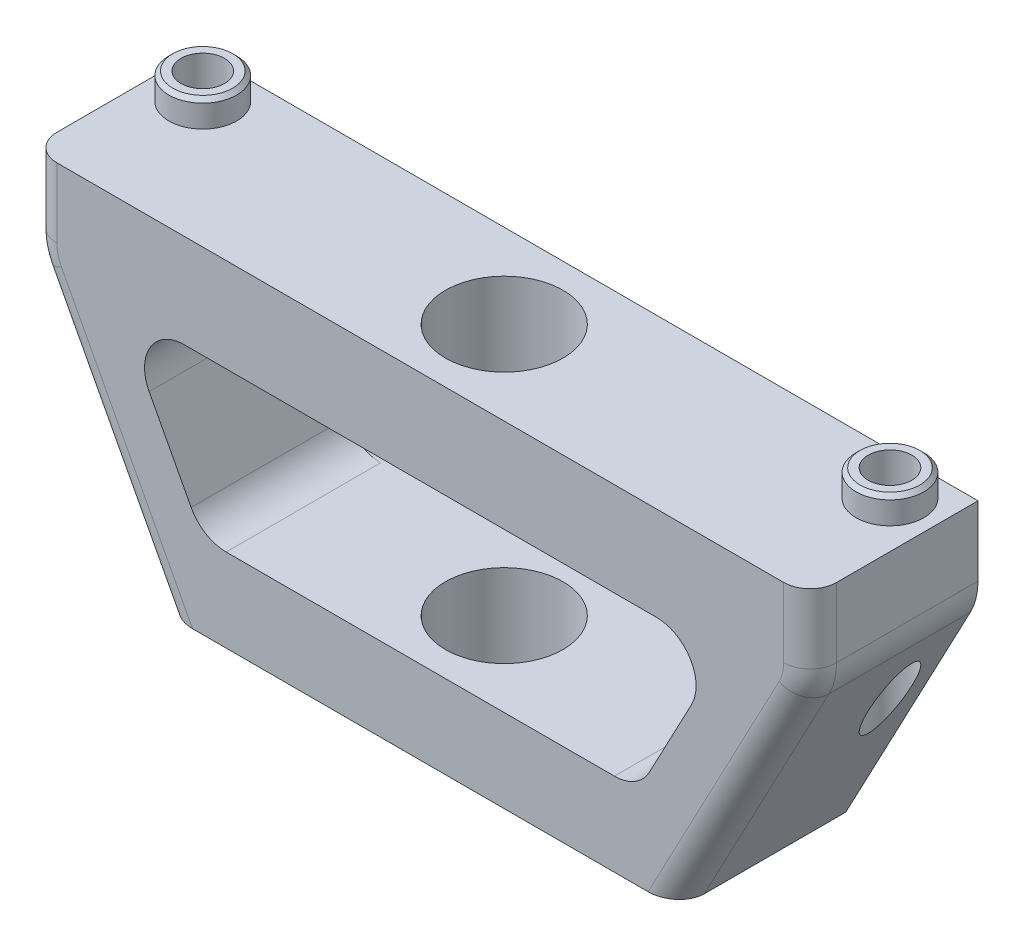
SolidWorks part; units mm, degrees
ref_plane "Front Plane" through (0, 0, 0) normal (0, 0, 1) x (1, 0, 0)
ref_plane "Top Plane" through (0, 0, 0) normal (0, 1, 0) x (1, 0, 0)
ref_plane "Right Plane" through (0, 0, 0) normal (1, 0, 0) x (0, 0, -1)
sketch "Sketch1" plane through (0, 0, 0) normal (0, 0, 1) x (1, 0, 0)
  line L0 (0, 0) -> (0, 26480.0211) construction
  line L1 (-29.5, 0) -> (29.5, 0)
  line L2 (29.5, 0) -> (29.5, -6.5)
  line L3 (29.5, -6.5) -> (19.5, -25.4)
  line L4 (19.5, -25.4) -> (-19.5, -25.4)
  line L5 (-19.5, -25.4) -> (-29.5, -6.5)
  line L6 (-29.5, -6.5) -> (-29.5, 0)
  point P5 (0, 0)
  point P10 (0, -25.4)
  dimension "D1" = 59
  dimension "D2" = 25.4
  dimension "D3" = 6.5
  dimension "D4" = 39
extrude "Boss-Extrude1" add sketch "Sketch1" along normal mid plane 12.7
sketch "Sketch2" plane through (0, 0, 0) normal (0, 0, 1) x (1, 0, 0)
  line L9 (-24.5502, -3.881) -> (-14.5502, -22.781)
  line L10 (-24.5502, -3.881) -> (-14.5502, -22.781) construction
  line L12 (-19.5, -19.1) -> (19.5, -19.1)
  line L13 (-19.5, -19.1) -> (19.5, -19.1) construction
  line L15 (14.5502, -22.781) -> (24.5502, -3.881)
  line L16 (14.5502, -22.781) -> (24.5502, -3.881) construction
  line L17 (-22.847, -7.1) -> (-16.4978, -19.1)
  line L18 (29.5, -7.1) -> (-29.5, -7.1)
  line L19 (29.5, -7.1) -> (-29.5, -7.1) construction
  line L20 (-16.4978, -19.1) -> (16.4978, -19.1)
  line L21 (16.4978, -19.1) -> (22.847, -7.1)
  line L22 (22.847, -7.1) -> (-22.847, -7.1)
  dimension "D1" = 5.6
  dimension "D2" = 6.3
  dimension "D3" = 5.6
  dimension "D4" = 7.1
extrude "Cut-Extrude1" cut sketch "Sketch2" against normal through all both and the other way through all
sketch "Sketch3" plane through (0, 0, 0) normal (0, 1, 0) x (1, 0, 0)
  circle A0 centre (0, 0) radius 4.45
  dimension "D1" = 8.9
extrude "Cut-Extrude2" cut sketch "Sketch3" against normal through all
fillet "Fillet1" radius 3 4 edges at (22.847, -7.1, 0) (16.4978, -19.1, 0) (-22.847, -7.1, 0) (-16.4978, -19.1, 0)
fillet "Fillet2" radius 5 2 edges at (29.5, -6.5, 0) (-29.5, -6.5, 0)
sketch "Sketch4" plane through (0, 0, 0) normal (0, 1, 0) x (1, 0, 0)
  line L0 (29.5, 6.35) -> (-29.5, 6.35) construction
  line L1 (0, 0) -> (0, 50000) construction
  circle A0 centre (-26, 3.19) radius 1.65
  circle A1 centre (-26, 3.19) radius 2.565
  circle A2 centre (26, 3.19) radius 1.65
  circle A3 centre (26, 3.19) radius 2.565
  dimension "D1" = 3.3
  dimension "D2" = 5.13
  dimension "D3" = 3.16
  dimension "D4" = 52
extrude "Boss-Extrude2" add sketch "Sketch4" along normal blind 2
sketch "Sketch5" plane through (0, 0, 0) normal (0, 1, 0) x (1, 0, 0)
  circle A0 centre (26, 3.19) radius 1.65 construction
  circle A1 centre (-26, 3.19) radius 1.65 construction
  circle A2 centre (26, 3.19) radius 1.65
  circle A3 centre (-26, 3.19) radius 1.65
extrude "Cut-Extrude3" cut sketch "Sketch5" against normal through all
sketch "Sketch6" plane through (0, 0, -6.35) normal (0, 0, -1) x (-1, 0, 0)
  line L0 (0, 0) -> (0, 50000) construction
  line L1 (17.75, -16.1) -> (-17.75, -16.1) construction
  line L2 (17.75, -19.1) -> (-17.75, -19.1)
  line L3 (17.75, -13.1) -> (-17.75, -13.1)
  line L4 (14.691, -19.1) -> (-14.691, -19.1) construction
  arc A0 (17.75, -19.1) -> (17.75, -13.1) centre (17.75, -16.1) ccw
  arc A1 (-17.75, -13.1) -> (-17.75, -19.1) centre (-17.75, -16.1) ccw
  point P5 (0, -16.1)
  dimension "D1" = 3
  dimension "D2" = 35.5
extrude "Cut-Extrude4" cut sketch "Sketch6" against normal blind 1
fillet "Fillet3" radius 2 6 edges at (24.2098, -16.4986, 6.35) (29.3527, -6.4634, 6.35) (-24.2098, -16.4986, 6.35) (-29.3527, -6.4634, 6.35) (29.5, -2.6294, 6.35) (-29.5, -2.6294, 6.35)
chamfer "Chamfer1" distance 0.3 angle 45 2 edges at (26, 2, -0.625) (-26, 2, -0.625)
